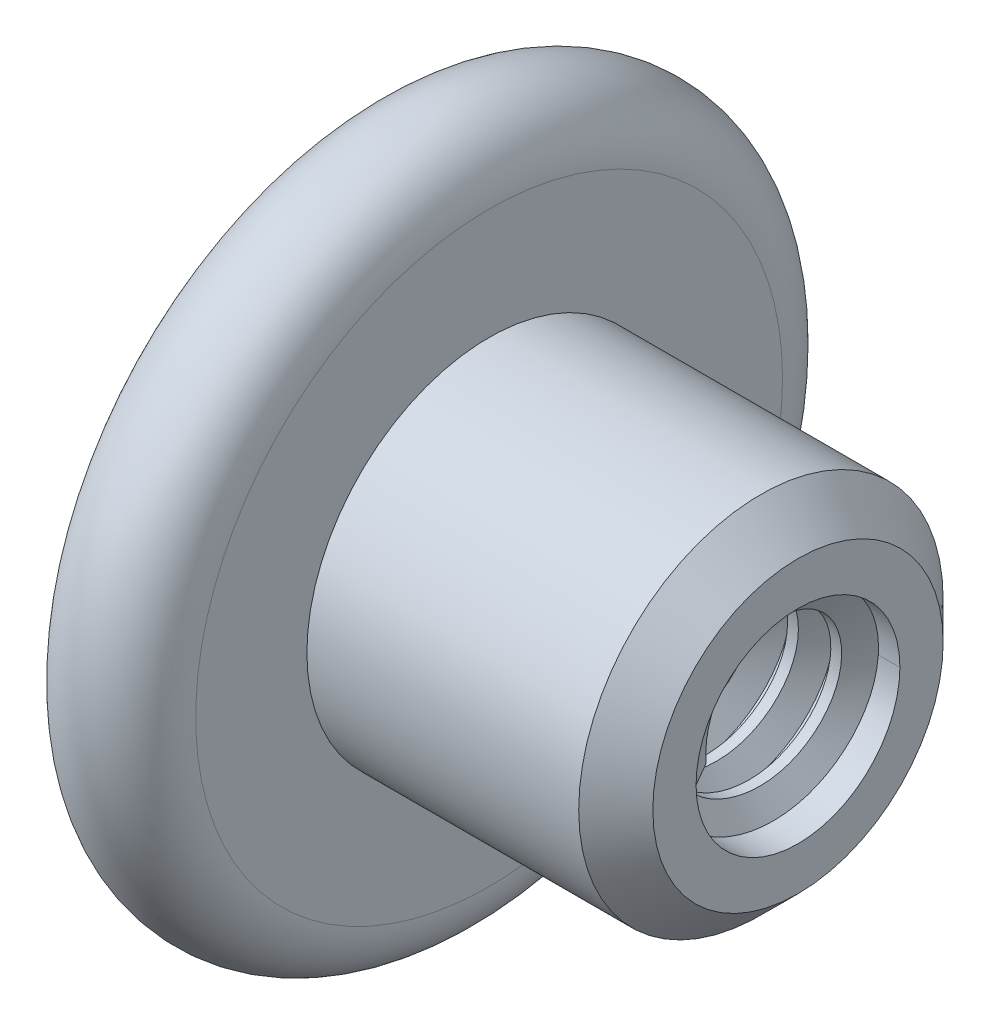
SolidWorks part; units mm, degrees
material "Plain Carbon Steel"
ref_plane "Front Plane" through (0, 0, 0) normal (0, 0, 1) x (1, 0, 0)
ref_plane "Top Plane" through (0, 0, 0) normal (0, 1, 0) x (1, 0, 0)
ref_plane "Right Plane" through (0, 0, 0) normal (1, 0, 0) x (0, 0, -1)
sketch "Sketch2" plane through (0, 0, 0) normal (0, 0, 1) x (1, 0, 0)
  line L0 (0, 0) -> (0, 3.45)
  line L1 (0, 3.45) -> (0.5, 2.95)
  line L2 (0.5, 2.95) -> (6.9, 2.95) construction
  line L3 (6.9, 2.95) -> (7.5, 2.35)
  line L4 (7.5, 2.35) -> (7.5, 0)
  line L5 (7.5, 0) -> (0, 0)
  line L6 (0.5, 2.95) -> (0.5, 4.75)
  line L7 (0.5, 4.75) -> (2.5, 4.75) construction
  line L8 (2.5, 4.75) -> (2.5, 2.95)
  line L9 (2.5, 2.95) -> (6.9, 2.95)
  arc A0 (0.5, 4.75) -> (2.5, 4.75) centre (1.5, 4.75) cw
  point P12 (1.0229, 3.2386)
  dimension "D1" = 7.5
  dimension "D2" = 0.5
  dimension "D3" = 45
  dimension "D4" = 2.95
  dimension "D5" = 0.6
  dimension "D6" = 1.8
  dimension "D7" = 2
revolve "Revolve1" add sketch "Sketch2" angle 360 about L5
hole_wizard "Tap Drill for M4 Tap1" positions "Sketch3" profile "Sketch4" hole size "M4" standard "ISO" end condition through all
sketch "Sketch3" plane through (7.5, 0, 0) normal (1, 0, 0) x (0, 0, -1)
  point P0 (0, 0)
sketch "Sketch4" plane through (7.5, 0, 0) normal (0, 1, 0) x (0, 0, -1)
  line L0 (0, 0) -> (0, 7.5)
  line L1 (0, 7.5) -> (1.65, 7.5)
  line L2 (1.65, 7.5) -> (1.65, 0)
  line L5 (1.65, 0) -> (0, 0)
  line L11 (0, -6.35) -> (0, 107.95) construction
  dimension "Thru Hole Dia." = 3.3
  dimension "Thru Hole Depth" = 7.5
thread "Thread1" pitch 0.7 method extrude profile "Thread Profile1" start angle 0, offset 0, length 4, pitch 0.7, diameter 3.3
ref_plane "Plane1" through (7.5, 0, 1.65) normal (0, -1, 0) x (0, 0, 1)
sketch "Thread Profile1" plane through (7.5, 0, 1.65) normal (0, -1, 0) x (0, 0, 1)
  line L0 (0, 0) -> (0, 0.7) construction
  line L11 (0, 0) -> (0, 0.6125)
  line L12 (0, 0.6125) -> (-0.3789, 0.3937)
  line L13 (-0.3789, 0.3937) -> (-0.3789, 0.2187)
  line L15 (-0.3789, 0.2187) -> (0, 0)
  line L17 (-0.3789, 0.3062) -> (0, 0.3062) construction
  point P2 (0, 0)
  dimension "Pitch" = 0.7
  dimension "Profile_Angle" = 60
  dimension "Profile_Land" = 0.175
  dimension "Profile_Height" = 0.3789
